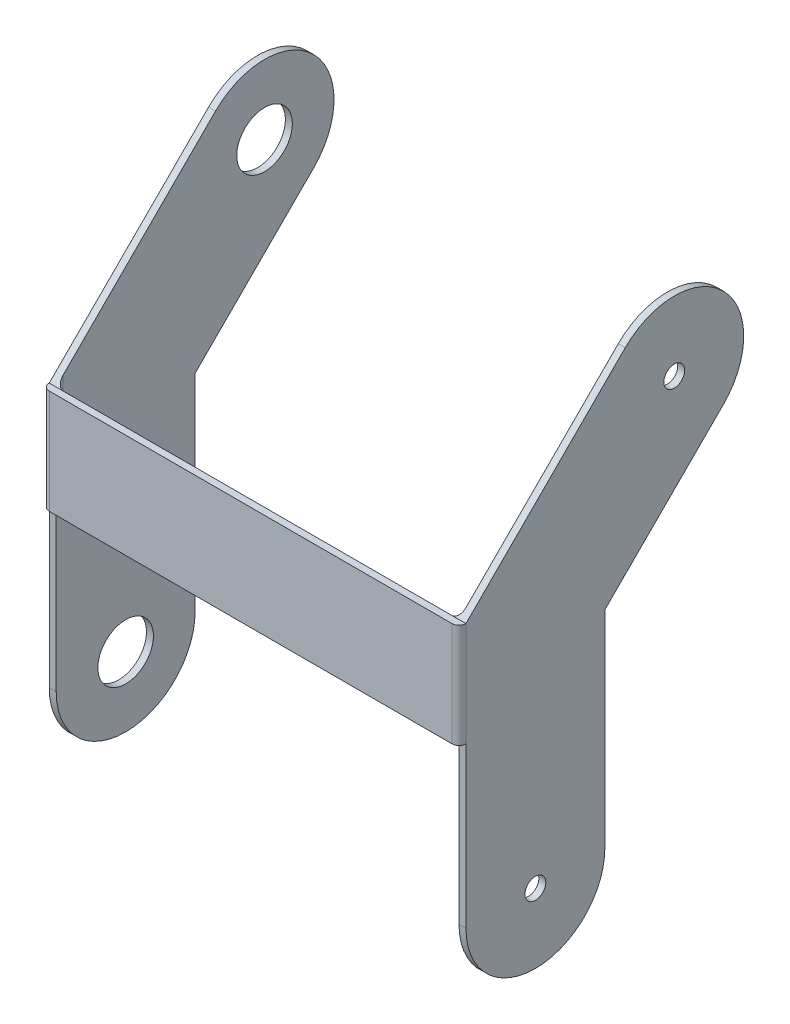
SolidWorks part; units mm, degrees
ref_plane "Front Plane" through (0, 0, 0) normal (0, 0, 1) x (1, 0, 0)
ref_plane "Top Plane" through (0, 0, 0) normal (0, 1, 0) x (1, 0, 0)
ref_plane "Right Plane" through (0, 0, 0) normal (1, 0, 0) x (0, 0, -1)
sketch "Sketch1" plane through (0, 0, 0) normal (1, 0, 0) x (0, 0, -1)
  line L0 (0, 0) -> (22.9286, 22.9286)
  line L1 (37.0708, 8.7865) -> (20, -8.2843)
  line L2 (20, -8.2843) -> (20, -38.019)
  line L3 (0, -38.019) -> (0, 0)
  line L4 (22.9286, 22.9286) -> (37.0708, 8.7865) construction
  arc A0 (22.9286, 22.9286) -> (37.0708, 8.7865) centre (29.9997, 15.8576) cw
  arc A1 (20, -38.019) -> (0, -38.019) centre (10, -38.019) cw
  circle A2 centre (29.9997, 15.8576) radius 1.5
  circle A3 centre (10, -38.019) radius 1.5
  dimension "D1" = 135
  dimension "D2" = 10
  dimension "D3" = 10
  dimension "D6" = 3
  dimension "D7" = 3
  dimension "D4" = 32.426
  dimension "D5" = 38.019
extrude "Boss-Extrude1" add sketch "Sketch1" along normal blind 1
sketch "Sketch2" plane through (1, 0, 0) normal (1, 0, 0) x (0, 0, -1)
  line L1 (0, 0) -> (-1, 0)
  line L2 (0, 0) -> (0, -15)
  line L3 (0, -15) -> (-1, -15)
  line L4 (-1, 0) -> (-1, -15)
  dimension "D1" = 15
  dimension "D2" = 1
extrude "Boss-Extrude2" add sketch "Sketch2" along normal blind 30 from offset 1 offset against normal yes
ref_plane "Plane1" through (30, 0, 0) normal (-1, 0, 0) x (0, 0, 1)
mirror "Mirror2" about plane through (30, 0, 0) normal (-1, 0, 0) of "Boss-Extrude2", "Boss-Extrude1"
fillet "Fillet1" radius 1 4 edges at (1, -7.5, 0) (59, -7.5, 0) (0, -7.5, 1) (60, -7.5, 1)
sketch "Sketch3" plane through (0, 0, 0) normal (-1, 0, 0) x (0, 0, 1)
  circle A0 centre (-29.9997, 15.8576) radius 4
  circle A1 centre (-10, -38.019) radius 4
  dimension "D1" = 8
  dimension "D2" = 8
extrude "Cut-Extrude1" cut sketch "Sketch3" against normal up to next
ref_axis "Axis1" through (36.9347, 15.8576, -29.9997) along (-1, 0, 0)
ref_axis "Axis2" through (43.8872, -38.019, -10) along (-1, 0, 0)
ref_plane "Plane2" through (0, -7.8671, -21.1928) normal (0, -0.348, -0.9375) x (-1, 0, 0)
